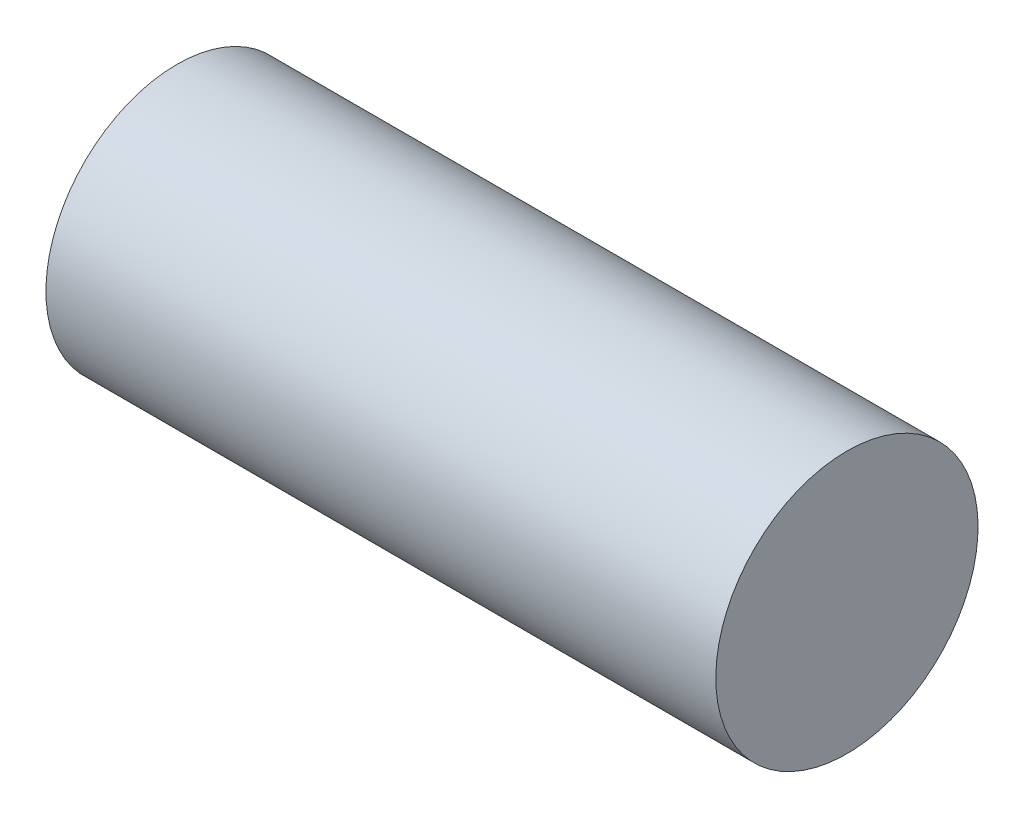
SolidWorks part; units mm, degrees
ref_plane "Front Plane" through (0, 0, 0) normal (0, 0, 1) x (1, 0, 0)
ref_plane "Top Plane" through (0, 0, 0) normal (0, 1, 0) x (1, 0, 0)
ref_plane "Right Plane" through (0, 0, 0) normal (1, 0, 0) x (0, 0, -1)
sketch "Sketch1" plane through (8, 0, 0) normal (1, 0, 0) x (0, 0, -1)
  line L0 (23.7464, -17.544) -> (20.3834, -17.544)
  line L1 (23.7464, -18.044) -> (20.3834, -18.044)
  line L2 (22.0649, -17.544) -> (22.0649, -18.044) construction
  line L3 (23.5649, -19.794) -> (20.5649, -19.794) construction
  line L4 (23.6141, -19.944) -> (20.5157, -19.944)
  line L5 (23.8537, -20.744) -> (20.276, -20.744)
  arc A0 (22.0649, -15.294) -> (20.5649, -19.794) centre (22.0649, -17.794) ccw construction
  circle A1 centre (22.0649, -17.794) radius 1.6 construction
  arc A2 (23.5649, -19.794) -> (22.0649, -15.294) centre (22.0649, -17.794) ccw construction
  arc A3 (22.0649, -15.294) -> (20.5649, -19.794) centre (22.0649, -17.794) ccw construction
  circle A4 centre (22.0649, -17.794) radius 1.6 construction
  arc A5 (23.5649, -19.794) -> (22.0649, -15.294) centre (22.0649, -17.794) ccw construction
  circle A6 centre (22.0649, -17.794) radius 1.45
  circle A7 centre (22.0649, -17.794) radius 1.7
  arc A8 (22.0649, -15.144) -> (20.5157, -19.944) centre (22.0649, -17.794) ccw
  arc A9 (23.6141, -19.944) -> (22.0649, -15.144) centre (22.0649, -17.794) ccw
  arc A10 (22.0649, -14.344) -> (20.276, -20.744) centre (22.0649, -17.794) ccw
  arc A11 (23.8537, -20.744) -> (22.0649, -14.344) centre (22.0649, -17.794) ccw
  circle A12 centre (22.0649, -17.794) radius 3.45
  dimension "D1" = 0.15
  dimension "D2" = 3.4
  dimension "D3" = 180
  dimension "D4" = 0.5
  dimension "D5" = 0.15
  dimension "D6" = 0.8
extrude "Boss-Extrude1" add sketch "Sketch1" against normal blind 17 from offset 0.2 contours L5 A11 A10 A9 L4 A8 | L5 A12 region at (8, -20.9453, -22.0649) region at (8, -20.6499, -22.0649)
extrude "Boss-Extrude2" add sketch "Sketch1<3>" along normal offset from surface (0.825 mm away) 0.2 contours A10 L5 A11 | A12
sketch "Sketch1<3>" plane through (8, 0, 0) normal (1, 0, 0) x (0, 0, -1) same geometry as "Sketch1"
